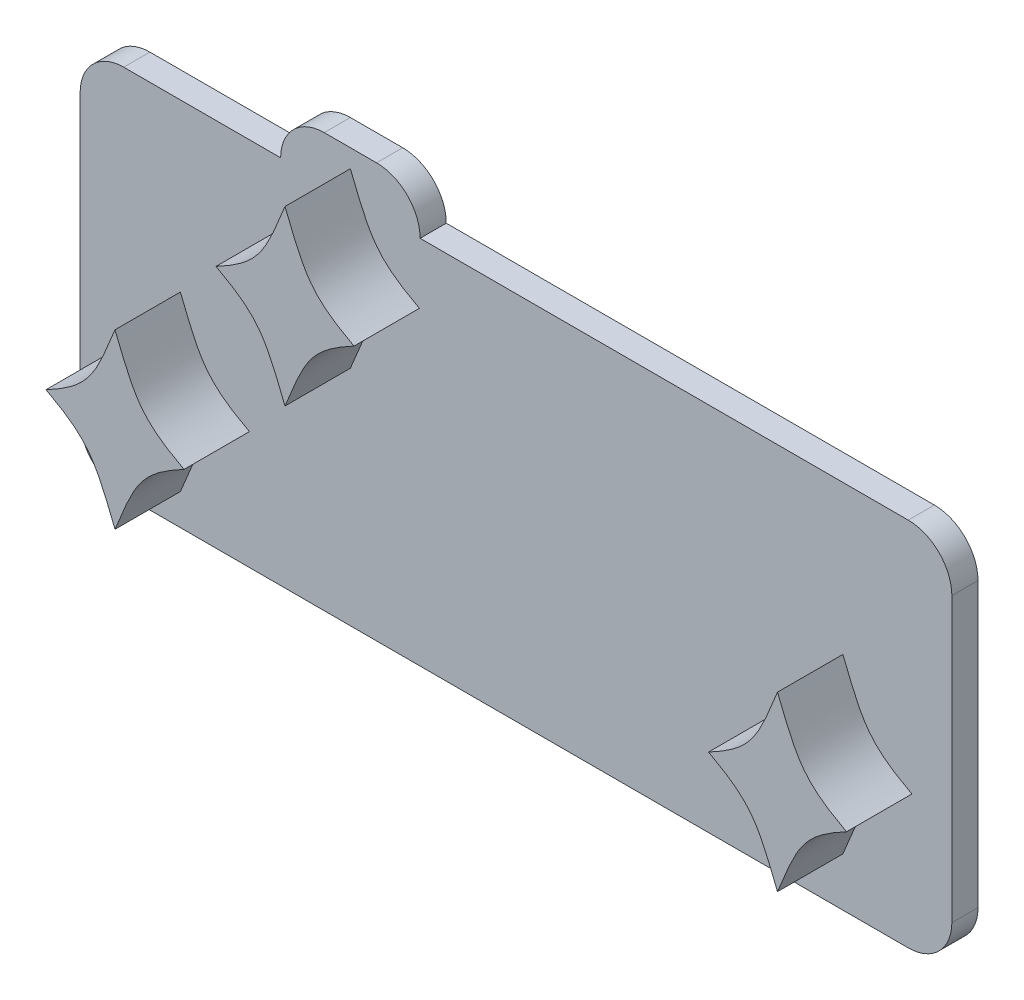
SolidWorks part; units mm, degrees
ref_plane "Front Plane" through (0, 0, 0) normal (0, 0, 1) x (1, 0, 0)
ref_plane "Top Plane" through (0, 0, 0) normal (0, 1, 0) x (1, 0, 0)
ref_plane "Right Plane" through (0, 0, 0) normal (1, 0, 0) x (0, 0, -1)
sketch "Sketch1" plane through (0, 0, 0) normal (0, 0, 1) x (1, 0, 0)
  line L1 (-2.8, 9.6) -> (-1, 9.6) construction
  line L2 (-2.8, 11.85) -> (-2.8, 9.6) construction
  line L3 (1.8512, 8.1472) -> (-3.8512, 11.0528) construction
  line L4 (-1.1143, 7.6777) -> (-4.4857, 16.0223) construction
  line L5 (23.35, 0) -> (15.6, 0) construction
  line L6 (8.5, 7.85) -> (8.5, 5.6) construction
  line L10 (8.5, 5.6) -> (10.3, 5.6) construction
  line L11 (10.1857, 3.6777) -> (6.8143, 12.0223) construction
  line L12 (13.1512, 4.1472) -> (7.4488, 7.0528) construction
  line L13 (0, 0) -> (15.6, 0) construction
  line L15 (-6.7, 7.45) -> (-6.7, 5.2) construction
  line L16 (-6.7, 5.2) -> (-4.9, 5.2) construction
  line L21 (-9.447, 14.2491) -> (-12.8185, 22.5938) construction
  line L22 (-9.2271, 7.4048) -> (-14.9295, 10.3103) construction
  line L23 (0, 0) -> (0, 15.7988) construction
  spline S0 degree 3 poles (-6.7, 7.45) (-6.1381, 6.0592) (-6.088, 5.8053) (-4.9, 5.2) knots 0 0 0 0 1 1 1 1 construction
  spline S1 degree 3 poles (-6.7, 7.45) (-7.2619, 6.0592) (-7.312, 5.8053) (-8.5, 5.2) knots 0 0 0 0 1 1 1 1 construction
  spline S2 degree 3 poles (-6.7, 2.95) (-6.1381, 4.3408) (-6.088, 4.5947) (-4.9, 5.2) knots 0 0 0 0 1 1 1 1 construction
  spline S3 degree 3 poles (-6.7, 2.95) (-7.2619, 4.3408) (-7.312, 4.5947) (-8.5, 5.2) knots 0 0 0 0 1 1 1 1 construction
  spline S4 degree 3 poles (-2.8, 11.85) (-2.2381, 10.4592) (-2.188, 10.2053) (-1, 9.6) knots 0 0 0 0 1 1 1 1 construction
  spline S5 degree 3 poles (-2.8, 11.85) (-3.3619, 10.4592) (-3.412, 10.2053) (-4.6, 9.6) knots 0 0 0 0 1 1 1 1 construction
  spline S6 degree 3 poles (-2.8, 7.35) (-3.3619, 8.7408) (-3.412, 8.9947) (-4.6, 9.6) knots 0 0 0 0 1 1 1 1 construction
  spline S7 degree 3 poles (-2.8, 7.35) (-2.2381, 8.7408) (-2.188, 8.9947) (-1, 9.6) knots 0 0 0 0 1 1 1 1 construction
  spline S8 degree 3 poles (8.5, 7.85) (9.0619, 6.4592) (9.112, 6.2053) (10.3, 5.6) knots 0 0 0 0 1 1 1 1 construction
  spline S9 degree 3 poles (8.5, 3.35) (9.0619, 4.7408) (9.112, 4.9947) (10.3, 5.6) knots 0 0 0 0 1 1 1 1 construction
  spline S10 degree 3 poles (8.5, 3.35) (7.9381, 4.7408) (7.888, 4.9947) (6.7, 5.6) knots 0 0 0 0 1 1 1 1 construction
  spline S11 degree 3 poles (8.5, 7.85) (7.9381, 6.4592) (7.888, 6.2053) (6.7, 5.6) knots 0 0 0 0 1 1 1 1 construction
  spline S12 degree 1 poles (8.5, 7.5823) (6.9167, 5.6) knots 0 0 1 1 construction
  spline S13 degree 1 poles (8.5, 3.6177) (6.9167, 5.6) knots 0 0 1 1 construction
  spline S14 degree 1 poles (8.5, 3.6177) (10.0833, 5.6) knots 0 0 1 1 construction
  spline S15 degree 1 poles (8.5, 7.5823) (10.0833, 5.6) knots 0 0 1 1 construction
  spline S16 degree 3 poles (8.5, 7.5823) (8.4481, 7.4531) (8.338, 7.1795) (8.1564, 6.7596) (7.9281, 6.3439) (7.6064, 6.0247) (7.2608, 5.7902) (7.0281, 5.6593) (6.9167, 5.6) knots 0.057905 0.057905 0.057905 0.057905 0.169422 0.280939 0.503973 0.727007 0.838524 0.950041 0.950041 0.950041 0.950041
  spline S17 degree 3 poles (6.9167, 5.6) (7.0281, 5.5407) (7.2608, 5.4098) (7.6064, 5.1753) (7.9281, 4.8561) (8.1564, 4.4404) (8.338, 4.0205) (8.4481, 3.7469) (8.5, 3.6177) knots 0.057905 0.057905 0.057905 0.057905 0.169422 0.280939 0.503973 0.727007 0.838524 0.950041 0.950041 0.950041 0.950041
  spline S18 degree 3 poles (8.5, 3.6177) (8.5519, 3.7469) (8.662, 4.0205) (8.8436, 4.4404) (9.0719, 4.8561) (9.3936, 5.1753) (9.7392, 5.4098) (9.9719, 5.5407) (10.0833, 5.6) knots 0.057905 0.057905 0.057905 0.057905 0.169422 0.280939 0.503973 0.727007 0.838524 0.950041 0.950041 0.950041 0.950041
  spline S19 degree 3 poles (10.0833, 5.6) (9.9719, 5.6593) (9.7392, 5.7902) (9.3936, 6.0247) (9.0719, 6.3439) (8.8436, 6.7596) (8.662, 7.1795) (8.5519, 7.4531) (8.5, 7.5823) knots 0.057905 0.057905 0.057905 0.057905 0.169422 0.280939 0.503973 0.727007 0.838524 0.950041 0.950041 0.950041 0.950041
  spline S20 degree 1 poles (-2.8, 7.6177) (-1.2167, 9.6) knots 0 0 1 1 construction
  spline S21 degree 1 poles (-2.8, 11.5823) (-1.2167, 9.6) knots 0 0 1 1 construction
  spline S22 degree 1 poles (-2.8, 11.5823) (-4.3833, 9.6) knots 0 0 1 1 construction
  spline S23 degree 1 poles (-2.8, 7.6177) (-4.3833, 9.6) knots 0 0 1 1 construction
  spline S24 degree 3 poles (-2.8, 7.6177) (-2.7481, 7.7469) (-2.638, 8.0205) (-2.4564, 8.4404) (-2.2281, 8.8561) (-1.9064, 9.1753) (-1.5608, 9.4098) (-1.3281, 9.5407) (-1.2167, 9.6) knots 0.057905 0.057905 0.057905 0.057905 0.169422 0.280939 0.503973 0.727007 0.838524 0.950041 0.950041 0.950041 0.950041
  spline S25 degree 3 poles (-1.2167, 9.6) (-1.3281, 9.6593) (-1.5608, 9.7902) (-1.9064, 10.0247) (-2.2281, 10.3439) (-2.4564, 10.7596) (-2.638, 11.1795) (-2.7481, 11.4531) (-2.8, 11.5823) knots 0.057905 0.057905 0.057905 0.057905 0.169422 0.280939 0.503973 0.727007 0.838524 0.950041 0.950041 0.950041 0.950041
  spline S26 degree 3 poles (-2.8, 11.5823) (-2.8519, 11.4531) (-2.962, 11.1795) (-3.1436, 10.7596) (-3.3719, 10.3439) (-3.6936, 10.0247) (-4.0392, 9.7902) (-4.2719, 9.6593) (-4.3833, 9.6) knots 0.057905 0.057905 0.057905 0.057905 0.169422 0.280939 0.503973 0.727007 0.838524 0.950041 0.950041 0.950041 0.950041
  spline S27 degree 3 poles (-4.3833, 9.6) (-4.2719, 9.5407) (-4.0392, 9.4098) (-3.6936, 9.1753) (-3.3719, 8.8561) (-3.1436, 8.4404) (-2.962, 8.0205) (-2.8519, 7.7469) (-2.8, 7.6177) knots 0.057905 0.057905 0.057905 0.057905 0.169422 0.280939 0.503973 0.727007 0.838524 0.950041 0.950041 0.950041 0.950041
  spline S28 degree 1 poles (-6.7, 7.1823) (-8.2833, 5.2) knots 0 0 1 1 construction
  spline S29 degree 1 poles (-6.7, 3.2177) (-8.2833, 5.2) knots 0 0 1 1 construction
  spline S30 degree 1 poles (-6.7, 3.2177) (-5.1167, 5.2) knots 0 0 1 1 construction
  spline S31 degree 1 poles (-6.7, 7.1823) (-5.1167, 5.2) knots 0 0 1 1 construction
  spline S32 degree 3 poles (-6.7, 7.1823) (-6.7519, 7.0531) (-6.862, 6.7795) (-7.0436, 6.3596) (-7.2719, 5.9439) (-7.5936, 5.6247) (-7.9392, 5.3902) (-8.1719, 5.2593) (-8.2833, 5.2) knots 0.057905 0.057905 0.057905 0.057905 0.169422 0.280939 0.503973 0.727007 0.838524 0.950041 0.950041 0.950041 0.950041
  spline S33 degree 3 poles (-8.2833, 5.2) (-8.1719, 5.1407) (-7.9392, 5.0098) (-7.5936, 4.7753) (-7.2719, 4.4561) (-7.0436, 4.0404) (-6.862, 3.6205) (-6.7519, 3.3469) (-6.7, 3.2177) knots 0.057905 0.057905 0.057905 0.057905 0.169422 0.280939 0.503973 0.727007 0.838524 0.950041 0.950041 0.950041 0.950041
  spline S34 degree 3 poles (-6.7, 3.2177) (-6.6481, 3.3469) (-6.538, 3.6205) (-6.3564, 4.0404) (-6.1281, 4.4561) (-5.8064, 4.7753) (-5.4608, 5.0098) (-5.2281, 5.1407) (-5.1167, 5.2) knots 0.057905 0.057905 0.057905 0.057905 0.169422 0.280939 0.503973 0.727007 0.838524 0.950041 0.950041 0.950041 0.950041
  spline S35 degree 3 poles (-5.1167, 5.2) (-5.2281, 5.2593) (-5.4608, 5.3902) (-5.8064, 5.6247) (-6.1281, 5.9439) (-6.3564, 6.3596) (-6.538, 6.7795) (-6.6481, 7.0531) (-6.7, 7.1823) knots 0.057905 0.057905 0.057905 0.057905 0.169422 0.280939 0.503973 0.727007 0.838524 0.950041 0.950041 0.950041 0.950041
  dimension "D4" = 3.6
  dimension "D3" = 4.5
  dimension "D5" = 4
  dimension "D6" = 4.5
  dimension "D13" = 4.5
  dimension "D14" = 4
  dimension "D18" = 22
  dimension "D19" = 27
  dimension "D20" = 4
  dimension "D21" = 4.5
  dimension "D7" = 22
  dimension "D8" = 27
  dimension "D9" = 6.7
  dimension "D10" = 5.2
  dimension "D11" = 2.8
  dimension "D12" = 9.6
  dimension "D15" = 27
  dimension "D16" = 22
  dimension "D17" = 8.5
  dimension "D22" = 3.6
  dimension "D23" = 4.5
  dimension "D24" = 0.1
  dimension "D25" = 5.6
sketch "Sketch2" plane through (0, 0, 0) normal (0, 0, 1) x (1, 0, 0)
  line L0 (-9, 11) -> (-4.4, 11)
  line L5 (-4.4, 11) -> (-4.4, 12)
  line L6 (-4.4, 12) -> (-1.2, 12)
  line L7 (-1.2, 12) -> (-1.2, 11)
  line L8 (-1.2, 11) -> (11, 11)
  line L9 (11, 11) -> (11, 2.5)
  line L10 (11, 2.5) -> (-9, 2.5)
  line L11 (-9, 2.5) -> (-9, 11)
  line L12 (0, 0) -> (0, 15.7988) construction
  line L13 (0, 0) -> (15.6, 0) construction
  dimension "D1" = 1.2
  dimension "D2" = 3.2
  dimension "D3" = 12
  dimension "D4" = 11
  dimension "D5" = 11
  dimension "D6" = 9
  dimension "D7" = 2.5
extrude "Boss-Extrude1" add sketch "Sketch2" against normal blind 0.6
extrude "Boss-Extrude2" add sketch "Sketch1" along normal blind 1.5
fillet "Fillet1" radius 1 6 edges at (-9, 2.5, -0.3) (11, 2.5, -0.3) (11, 11, -0.3) (-1.2, 12, -0.3) (-4.4, 12, -0.3) (-9, 11, -0.3)
